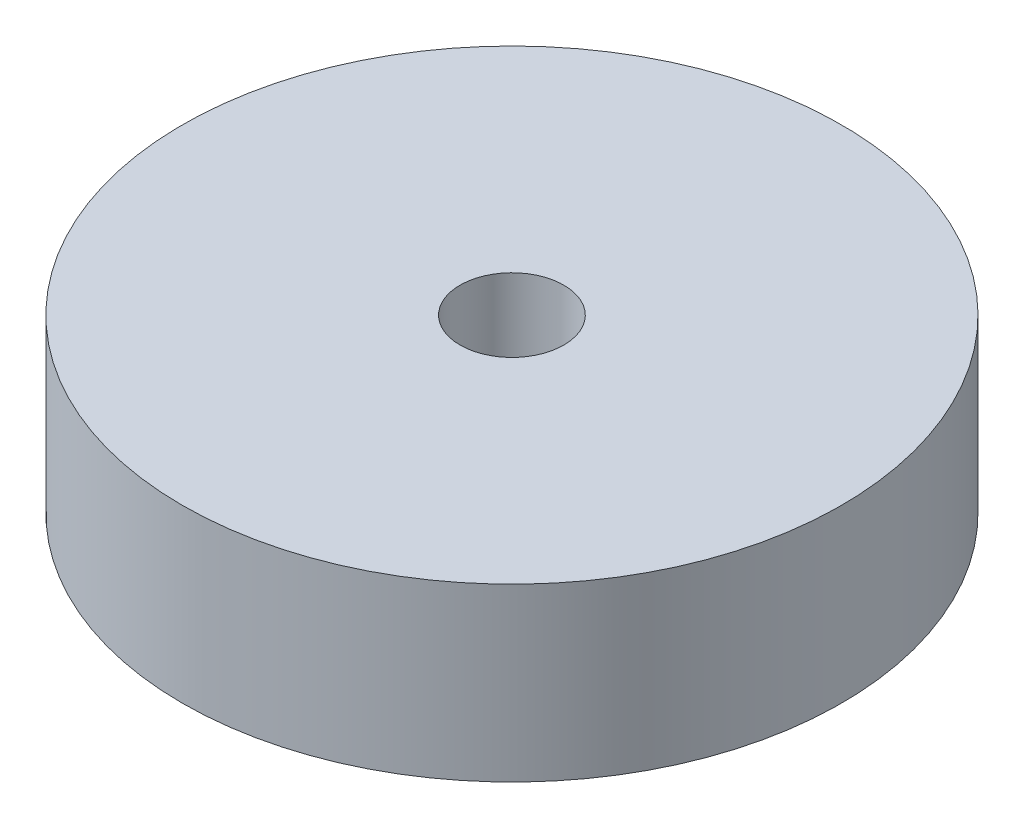
SolidWorks part; units mm, degrees
ref_plane "Front Plane" through (0, 0, 0) normal (0, 0, 1) x (1, 0, 0)
ref_plane "Top Plane" through (0, 0, 0) normal (0, 1, 0) x (1, 0, 0)
ref_plane "Right Plane" through (0, 0, 0) normal (1, 0, 0) x (0, 0, -1)
sketch "Sketch1" plane through (0, 0, 0) normal (0, 1, 0) x (1, 0, 0)
  circle A0 centre (0, 0) radius 317.5
  dimension "D1" = 635
extrude "Boss-Extrude1" add sketch "Sketch1" along normal blind 165.1
sketch "Sketch2" plane through (0, 165.1, 0) normal (0, 1, 0) x (1, 0, 0)
  circle A0 centre (0, 0) radius 50
  dimension "D1" = 100
extrude "Cut-Extrude1" cut sketch "Sketch2" against normal through all
